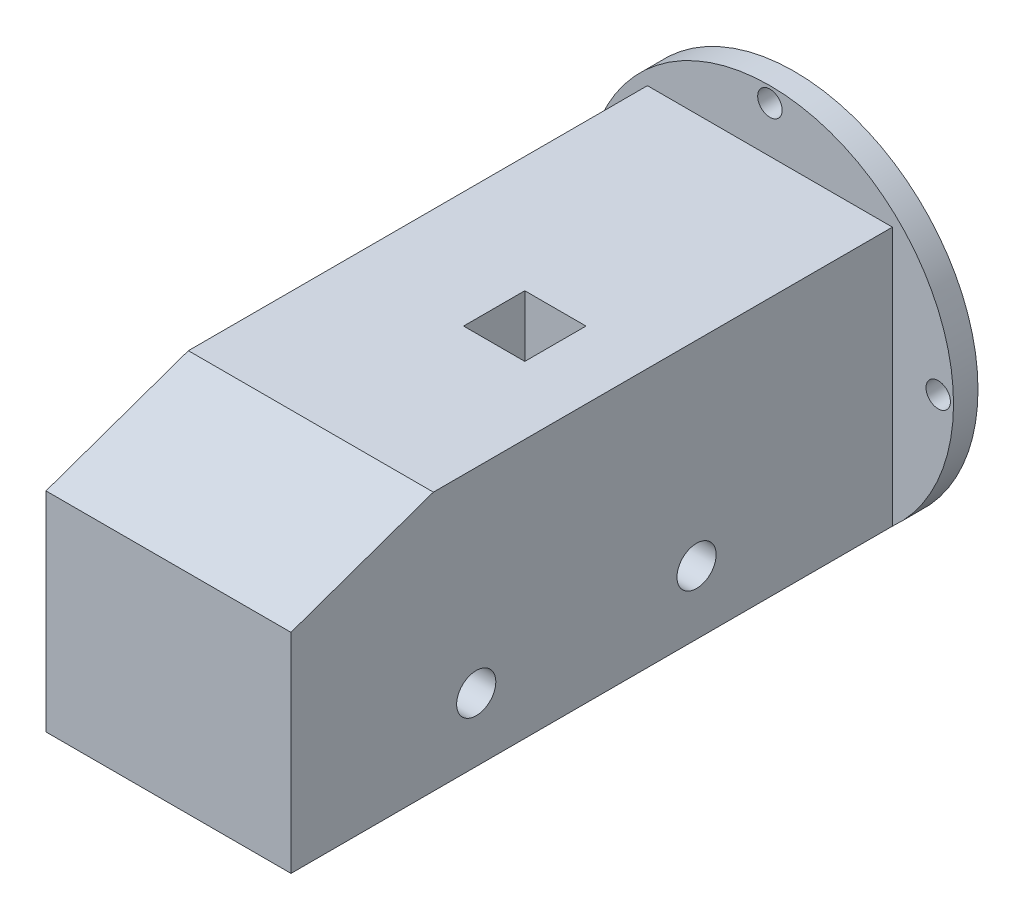
SolidWorks part; units mm, degrees
material "PLA"
ref_plane "Alzado" through (0, 0, 0) normal (0, 0, 1) x (1, 0, 0)
ref_plane "Planta" through (0, 0, 0) normal (0, 1, 0) x (1, 0, 0)
ref_plane "Vista lateral" through (0, 0, 0) normal (1, 0, 0) x (0, 0, -1)
sketch "Croquis1" plane through (0, 0, 0) normal (0, 0, 1) x (1, 0, 0)
  line L0 (0, 0) -> (25, 0) construction
  line L1 (25, 0) -> (30, 0) construction
  circle A0 centre (0, 0) radius 30
  circle A1 centre (0, 0) radius 25 construction
  circle A2 centre (27.5, 0) radius 1.999
  circle A3 centre (0, -27.5) radius 1.999
  circle A4 centre (-27.5, 0) radius 1.999
  circle A5 centre (0, 27.5) radius 1.999
  point P17 (0, 0)
  dimension "D1" = 4
extrude "Saliente-Extruir1" add sketch "Croquis1" along normal blind 4
sketch "Croquis2" plane through (0, 0, 4) normal (0, 0, 1) x (1, 0, 0)
  line L0 (0, 0) -> (0, 19.9742) construction
  line L1 (-20.0156, 19.9742) -> (20.0156, 19.9742)
  line L2 (20.0156, 19.9742) -> (20.0156, -22.3467)
  line L3 (20.0156, -22.3467) -> (-20.0156, -22.3467)
  line L4 (-20.0156, 19.9742) -> (-20.0156, -22.3467)
  circle A0 centre (0, 0) radius 30 construction
  point P9 (0, -22.3467)
extrude "Saliente-Extruir2" add sketch "Croquis2" along normal blind 150
sketch "Croquis3" plane through (-20.0156, 0, 0) normal (-1, 0, 0) x (0, 0, 1)
  line L0 (0, 0) -> (36, 0) construction
  line L1 (36, 0) -> (36, -11.961) construction
  line L3 (52, -11.961) -> (72, -11.961) construction
  circle A0 centre (36, -11.961) radius 20 construction
  circle A1 centre (36, -11.961) radius 16 construction
  circle A2 centre (72, -11.961) radius 20 construction
  circle A3 centre (36, -11.961) radius 3.2
  circle A4 centre (72, -11.961) radius 3.2
extrude "Cortar-Extruir1" cut sketch "Croquis3" against normal up to next contours A3 region at (-20.0156, -11.961, 36)
sketch "Croquis4" plane through (-20.0156, 0, 0) normal (-1, 0, 0) x (0, 0, 1)
  line L0 (72, -11.961) -> (60.0736, -11.961) construction
  line L1 (52, -11.961) -> (72, -11.961) construction
  line L2 (60.0736, -5.461) -> (60.0736, -18.461)
  line L3 (60.0736, -18.461) -> (93.4736, -18.461)
  line L4 (93.4736, -18.461) -> (93.4736, -5.461)
  line L5 (60.0736, -5.461) -> (93.4736, -5.461)
  line L6 (72, -11.961) -> (92.3811, -11.961) construction
  line L7 (72, -11.961) -> (60.0736, -11.961) construction
  line L8 (60.0736, -11.961) -> (60.0736, -9.5695) construction
  point P9 (93.4736, -11.961)
extrude "Cortar-Extruir2" cut sketch "Croquis4" against normal blind 12
sketch "Croquis5" plane through (-8.0156, 0, 0) normal (-1, 0, 0) x (0, 0, 1)
  line L6 (76.7736, -18.461) -> (87.3736, -18.461) construction
  line L11 (60.0736, -18.461) -> (76.7736, -18.461) construction
  line L12 (60.0736, -18.461) -> (93.4736, -18.461) construction
  line L13 (60.0736, -18.461) -> (93.4736, -18.461) construction
  line L14 (93.4736, -5.461) -> (60.0736, -5.461) construction
  line L15 (87.3736, -18.461) -> (66.1326, -18.461)
  line L16 (87.3736, -18.461) -> (87.3736, -5.461)
  line L17 (87.3736, -5.461) -> (66.1326, -5.461)
  line L18 (66.1326, -18.461) -> (66.1326, -5.461)
extrude "Cortar-Extruir3" cut sketch "Croquis5" against normal blind 17
sketch "Croquis6" plane through (-8.0156, 0, 0) normal (-1, 0, 0) x (0, 0, 1)
  line L1 (93.4736, -18.461) -> (93.4736, -5.461) construction
  line L3 (66.1326, -11.961) -> (60.0736, -11.961) construction
  line L6 (60.0736, -5.461) -> (60.0736, -18.461) construction
  line L8 (60.0736, -18.461) -> (66.1326, -18.461) construction
  line L9 (66.1326, -18.461) -> (66.1326, -11.961) construction
  line L10 (87.3736, -11.961) -> (93.4736, -11.961) construction
  line L11 (87.3736, -18.461) -> (87.3736, -5.461) construction
  circle A3 centre (63.1031, -11.961) radius 1
  circle A4 centre (90.4236, -11.961) radius 1
extrude "Cortar-Extruir4" cut sketch "Croquis6" against normal blind 5
sketch "Croquis7" plane through (-20.0156, 0, 0) normal (-1, 0, 0) x (0, 0, 1)
  line L0 (154, -22.3467) -> (102.2621, -22.3467)
  line L1 (154, -22.3467) -> (4, -22.3467) construction
  line L2 (102.2621, -22.3467) -> (102.2621, 11.7673)
  line L4 (154, 19.9742) -> (4, 19.9742) construction
  line L5 (79, 19.9742) -> (154, 19.9742)
  line L6 (154, 19.9742) -> (154, -22.3467)
  line L7 (79, 19.9742) -> (102.2621, 11.7673)
  line M9 (4, -22.3467) -> (154, -22.3467)
  line M11 (154, 19.9742) -> (4, 19.9742)
  line M15 (154, -22.3467) -> (154, 19.9742)
extrude "Cortar-Extruir6" cut sketch "Croquis7" against normal through all and the other way through all contours L7 L2 M11 M9 M15 region at (-20.0156, -0.4166, 126.7265)
sketch "Croquis10" plane through (20.0156, 0, 0) normal (1, 0, 0) x (0, 0, -1)
  circle A0 centre (-72, -11.961) radius 3.2
extrude "Cortar-Extruir10" cut sketch "Croquis10" against normal blind 10
sketch "Croquis11" plane through (0, 0, 66.1326) normal (0, 0, 1) x (1, 0, 0)
  line L0 (8.9844, -18.461) -> (-8.0156, -18.461) construction
  line L1 (8.9844, -5.461) -> (-5.0156, -5.461)
  line L2 (8.9844, -5.461) -> (8.9844, -18.461)
  line L3 (8.9844, -18.461) -> (-5.0156, -18.461)
  line L4 (-5.0156, -5.461) -> (-5.0156, -18.461)
extrude "Cortar-Extruir11" cut sketch "Croquis11" against normal blind 6.1
sketch "Croquis12" plane through (0, 0, 60.0326) normal (0, 0, 1) x (1, 0, 0)
  line L0 (8.9844, -11.961) -> (8.9844, -6.961) construction
  line L1 (8.9844, -18.461) -> (8.9844, -5.461) construction
  line L3 (8.9844, -6.961) -> (-1.0156, -6.961)
  line L4 (8.9844, -6.961) -> (8.9844, -16.9395)
  line L5 (8.9844, -16.9395) -> (-1.0156, -16.9395)
  line L6 (-1.0156, -6.961) -> (-1.0156, -16.9395)
extrude "Cortar-Extruir12" cut sketch "Croquis12" against normal blind 17
sketch "Croquis13" plane through (0, -6.961, 0) normal (0, -1, 0) x (1, 0, 0)
  line L1 (8.9844, 43.0326) -> (-1.0156, 43.0326)
  line L2 (8.9844, 43.0326) -> (8.9844, 53.0326)
  line L3 (8.9844, 53.0326) -> (-1.0156, 53.0326)
  line L4 (-1.0156, 43.0326) -> (-1.0156, 53.0326)
extrude "Cortar-Extruir13" cut sketch "Croquis13" against normal blind 45
sketch "Croquis14" plane through (0, 0, 53.0326) normal (0, 0, -1) x (-1, 0, 0)
  line L1 (-62.8807, 49.4376) -> (62.8807, 49.4376)
  line L2 (-62.8807, 49.4376) -> (-62.8807, -49.4376)
  line L3 (-62.8807, -49.4376) -> (62.8807, -49.4376)
  line L4 (62.8807, 49.4376) -> (62.8807, -49.4376)
  line L5 (-62.8807, 49.4376) -> (62.8807, -49.4376) construction
  line L6 (-62.8807, -49.4376) -> (62.8807, 49.4376) construction
  point P0 (0, 0)
sketch "Croquis15" plane through (-5.0156, 0, 0) normal (1, 0, 0) x (0, 0, -1)
  line L1 (-127.1279, 25.4022) -> (-30.0149, 25.4022)
  line L2 (-127.1279, 25.4022) -> (-127.1279, -30.379)
  line L3 (-127.1279, -30.379) -> (-30.0149, -30.379)
  line L4 (-30.0149, 25.4022) -> (-30.0149, -30.379)
  line L5 (-127.1279, 25.4022) -> (-30.0149, -30.379) construction
  line L6 (-127.1279, -30.379) -> (-30.0149, 25.4022) construction
  point P0 (-78.5714, -2.4884)
extrude "Cortar-Extruir18" cut sketch "Croquis11<3>" along normal blind 27.3
sketch "Croquis11<3>" plane through (0, 0, 66.1326) normal (0, 0, 1) x (1, 0, 0) same geometry as "Croquis11"
sketch "Croquis16" plane through (0, 0, 93.4326) normal (0, 0, -1) x (-1, 0, 0)
  line L1 (-24.6232, 27.6498) -> (9.0763, 27.6498)
  line L2 (-24.6232, 27.6498) -> (-24.6232, -25.9706)
  line L3 (-24.6232, -25.9706) -> (9.0763, -25.9706)
  line L4 (9.0763, 27.6498) -> (9.0763, -25.9706)
  line L5 (-24.6232, 27.6498) -> (9.0763, -25.9706) construction
  line L6 (-24.6232, -25.9706) -> (9.0763, 27.6498) construction
  point P0 (-7.7735, 0.8396)
